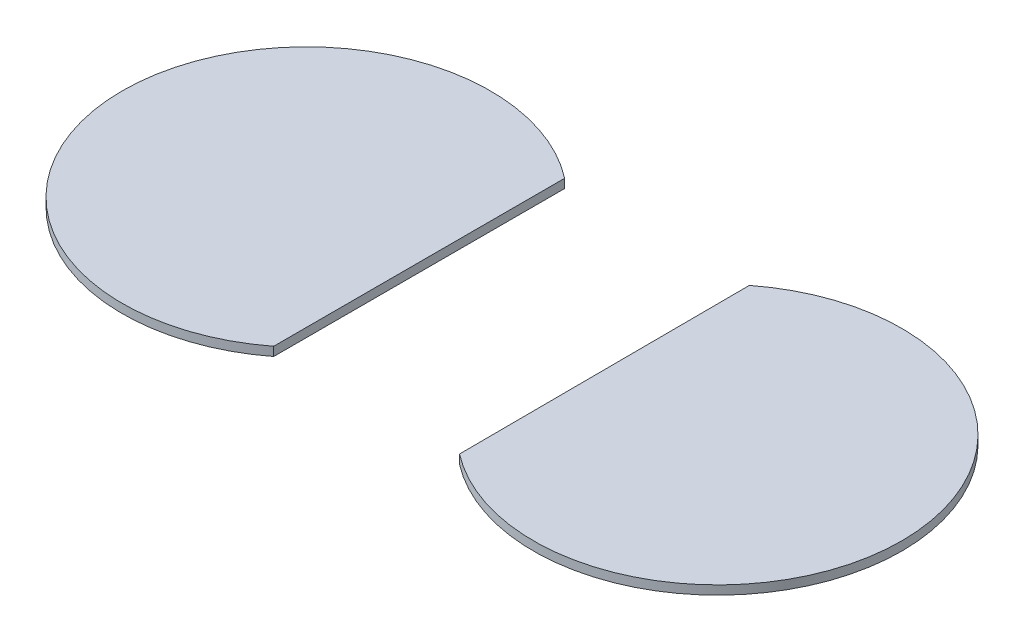
SolidWorks part; units mm, degrees
ref_plane "Front Plane" through (0, 0, 0) normal (0, 0, 1) x (1, 0, 0)
ref_plane "Top Plane" through (0, 0, 0) normal (0, 1, 0) x (1, 0, 0)
ref_plane "Right Plane" through (0, 0, 0) normal (1, 0, 0) x (0, 0, -1)
sketch "Sketch1" plane through (0, 0, 0) normal (0, 1, 0) x (1, 0, 0)
  line L0 (0, 0) -> (-15, 0) construction
  line L1 (-3.2, 4.899) -> (-3.2, -4.899)
  line L2 (3.0343, 4.8844) -> (3.0718, -4.9135)
  circle A0 centre (0, 0) radius 15
  circle A2 centre (-7, 0) radius 6.2
  circle A3 centre (0, 0) radius 10.75
  circle A4 centre (6.853, 0) radius 6.2
  dimension "D1" = 30
  dimension "D2" = 8
  dimension "D3" = 12.4
  dimension "D4" = 21.5
  dimension "D5" = 12.4
  dimension "D6" = 3.8
  dimension "D7" = 3.8
extrude "Boss-Extrude1" add sketch "Sketch1" along normal blind 0.3 contours L0 L1 A2 A3 | L1 L0 A3 A2 | A3 L0 A2 | L0 A3 A2 | A3 A4 L2 | A3 A4 region at (-6.774, 0, 2.8328) region at (-6.774, 0, -2.8328) region at (-11.3962, 0, 2.4268) region at (-11.3962, 0, -2.4268) region at (11.3442, 0, 0) region at (6.6983, 0, -0.0036)
